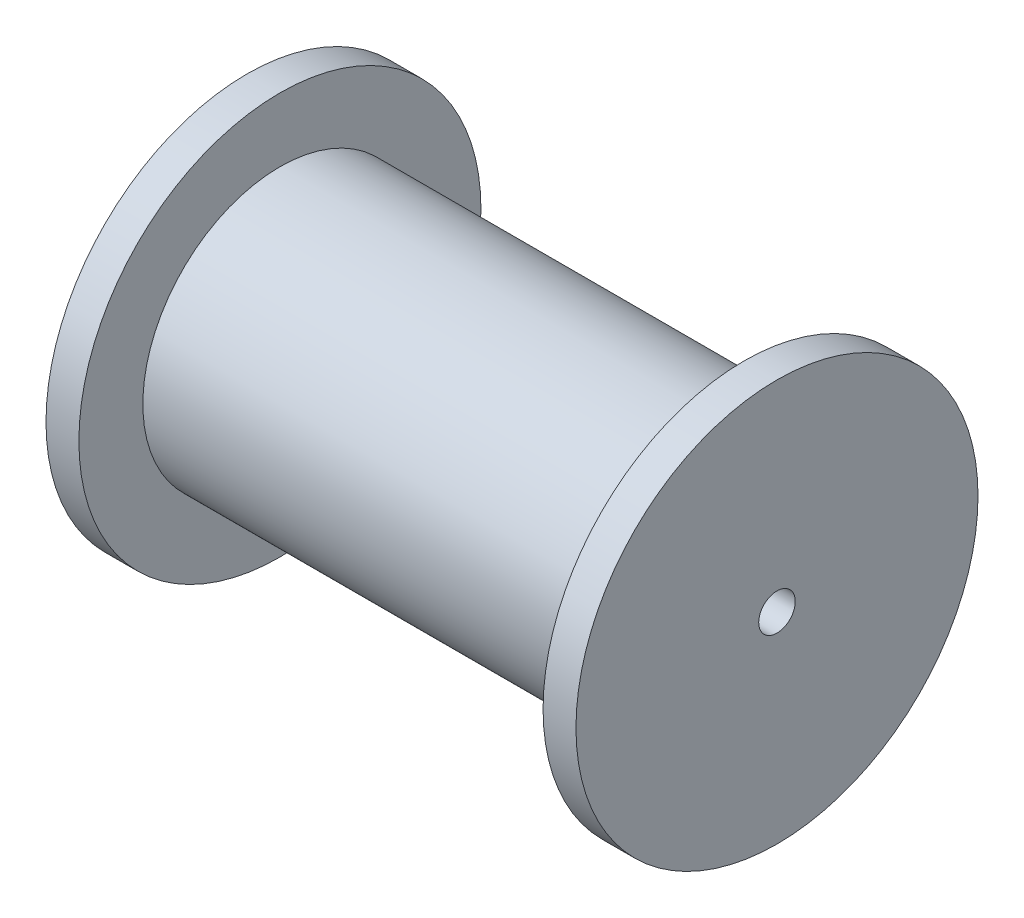
SolidWorks part; units mm, degrees
ref_plane "Front Plane" through (0, 0, 0) normal (0, 0, 1) x (1, 0, 0)
ref_plane "Top Plane" through (0, 0, 0) normal (0, 1, 0) x (1, 0, 0)
ref_plane "Right Plane" through (0, 0, 0) normal (1, 0, 0) x (0, 0, -1)
sketch "Sketch1" plane through (0, 0, 0) normal (0, 0, 1) x (1, 0, 0)
  line L0 (0, 15) -> (-58, 15)
  line L1 (0, 0) -> (-58, 0)
  line L2 (0, 0) -> (0, 15)
  line L4 (-58, 0) -> (-58, 15)
  line L6 (-58, 15) -> (0, 15)
  line L7 (-58, 15) -> (-58, 22)
  line L8 (-58, 22) -> (0, 22)
  line L9 (0, 15) -> (0, 22)
  line L10 (-54.4, 22) -> (-54.4, 15)
  line L11 (-29, 22) -> (-29, 15) construction
  line L12 (-3.6, 22) -> (-3.6, 15)
  dimension "D1" = 15
  dimension "D2" = 50.8
  dimension "D3" = 7
  dimension "D4" = 3.6
revolve "Revolve1" add sketch "Sketch1" angle 360 about L1 region at (-29, 7.5, 0) region at (-1.8, 18.5, 0) region at (-56.2, 18.5, 0)
sketch "Sketch2" plane through (-58, 0, 0) normal (-1, 0, 0) x (0, 0, 1)
  circle A0 centre (0, 0) radius 2
  dimension "D1" = 4
extrude "Cut-Extrude1" cut sketch "Sketch2" against normal through all
